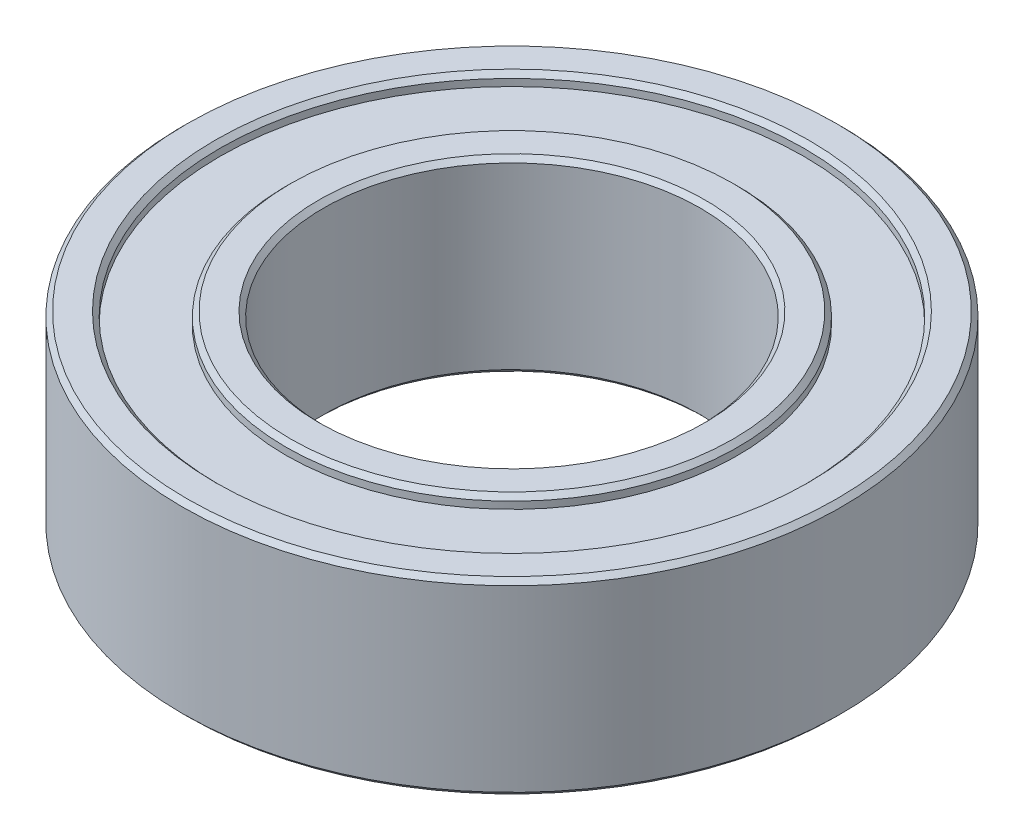
SolidWorks part; units mm, degrees
material "1023 Carbon Steel Sheet (SS)"
ref_plane "Front Plane" through (0, 0, 0) normal (0, 0, 1) x (1, 0, 0)
ref_plane "Top Plane" through (0, 0, 0) normal (0, 1, 0) x (1, 0, 0)
ref_plane "Right Plane" through (0, 0, 0) normal (1, 0, 0) x (0, 0, -1)
sketch "Sketch1" plane through (0, 0, 0) normal (0, 1, 0) x (1, 0, 0)
  circle A0 centre (0, 0) radius 7
  circle A1 centre (0, 0) radius 4
  circle A2 centre (0, 0) radius 4.8
  circle A3 centre (0, 0) radius 6.2
  dimension "D3" = 8
  dimension "D4" = 14
  dimension "D1" = 0.8
  dimension "D2" = 0.8
extrude "Boss-Extrude1" add sketch "Sketch1" along normal mid plane 4 contours A0 A3 | A2 A1 region at (-6.802, 0, 0) region at (-4.6642, 0, 0)
extrude "Boss-Extrude2" add sketch "Sketch1<3>" along normal mid plane 3.5 contours A3 A2 region at (-6.0246, 0, 0)
sketch "Sketch1<3>" plane through (0, 0, 0) normal (0, 1, 0) x (1, 0, 0) same geometry as "Sketch1"
chamfer "Chamfer2" distance 0.1 angle 45 4 edges at (0, -2, 4.8) (0, -2, 4) (0, 2, 4.8) (0, 2, 4)
chamfer "Chamfer3" distance 0.1 angle 45 4 edges at (0, 2, 6.2) (0, 2, 7) (0, -2, 6.2) (0, -2, 7)
equation "\"D1@Boss-Extrude2\"=\"D1@Boss-Extrude1\" - 0.5"
